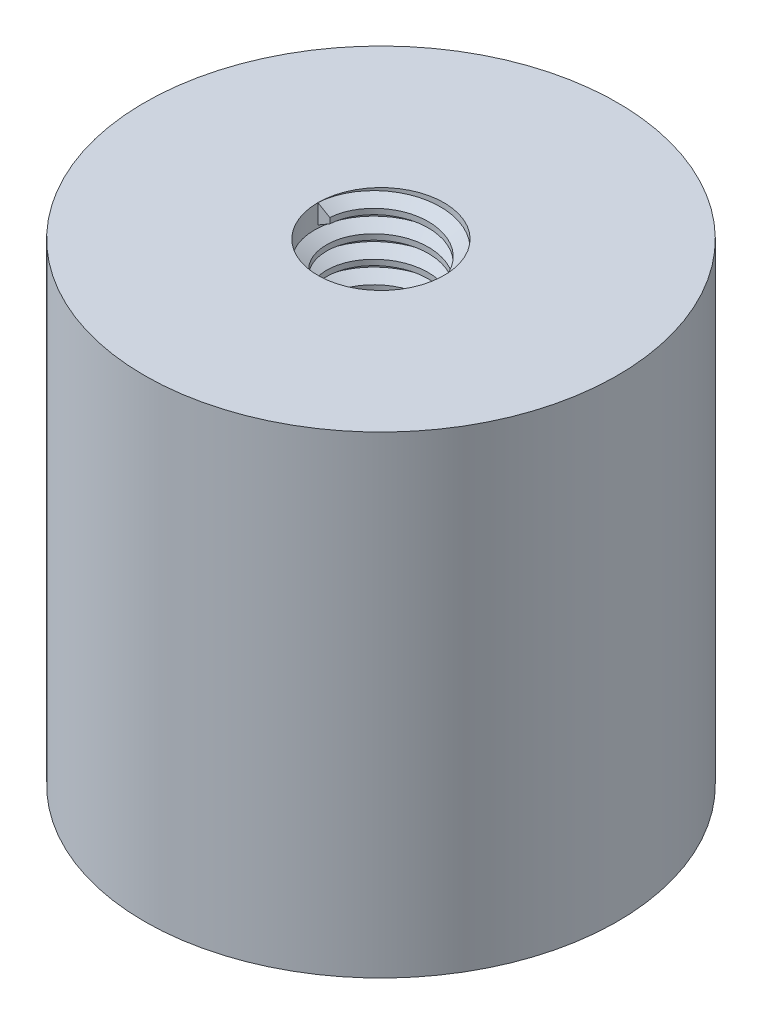
SolidWorks part; units mm, degrees
ref_plane "Front Plane" through (0, 0, 0) normal (0, 0, 1) x (1, 0, 0)
ref_plane "Top Plane" through (0, 0, 0) normal (0, 1, 0) x (1, 0, 0)
ref_plane "Right Plane" through (0, 0, 0) normal (1, 0, 0) x (0, 0, -1)
sketch "Sketch1" plane through (0, 0, 0) normal (0, 1, 0) x (1, 0, 0)
  circle A0 centre (0, 0) radius 7.5
  dimension "D1" = 15
extrude "Boss-Extrude1" add sketch "Sketch1" along normal blind 15
hole_wizard "Ø4.0mm Dowel Hole1" positions "Sketch2" profile "Sketch3" hole size "Ø4.0" standard "ANSI Metric"
sketch "Sketch2" plane through (0, 15, 0) normal (0, 1, 0) x (1, 0, 0)
  point P0 (0, 0)
sketch "Sketch3" plane through (0, 15, 0) normal (1, 0, 0) x (0, 0, 1)
  line L0 (0, 0) -> (0, 8.2017)
  line L1 (0, 8.2017) -> (2, 7)
  line L2 (2, 7) -> (2, 0)
  line L5 (2, 0) -> (0, 0)
  line L10 (0, 8.2017) -> (-2, 7) construction
  line L11 (0, -6.35) -> (0, 107.95) construction
  dimension "Hole Dia." = 4
  dimension "Hole Depth" = 7
  dimension "Drill Angle" = 118
thread "Thread1" pitch 0.7 method extrude profile "Thread Profile1" start angle 0, offset 0, length 0, pitch 0.7, diameter 4
ref_plane "Plane1" through (-2, 15, 0) normal (0, 0, 1) x (-1, 0, 0)
sketch "Thread Profile1" plane through (-2, 15, 0) normal (0, 0, 1) x (-1, 0, 0)
  line L0 (0, 0) -> (0, 0.7) construction
  line L11 (0, 0) -> (0, 0.6125)
  line L12 (0, 0.6125) -> (-0.3789, 0.3937)
  line L13 (-0.3789, 0.3937) -> (-0.3789, 0.2187)
  line L15 (-0.3789, 0.2187) -> (0, 0)
  line L17 (-0.3789, 0.3062) -> (0, 0.3062) construction
  point P2 (0, 0)
  dimension "Pitch" = 0.7
  dimension "Profile_Angle" = 60
  dimension "Profile_Land" = 0.175
  dimension "Profile_Height" = 0.3789
